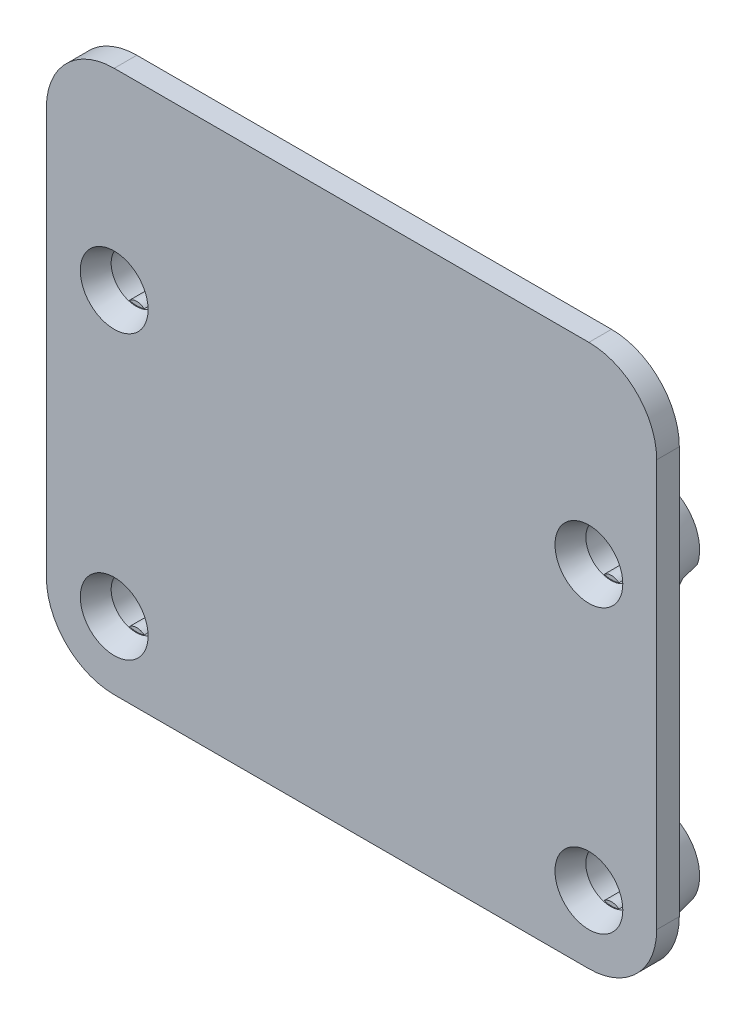
SolidWorks part; units mm, degrees
ref_plane "Front Plane" through (0, 0, 0) normal (0, 0, 1) x (1, 0, 0)
ref_plane "Top Plane" through (0, 0, 0) normal (0, 1, 0) x (1, 0, 0)
ref_plane "Right Plane" through (0, 0, 0) normal (1, 0, 0) x (0, 0, -1)
sketch "Sketch1" plane through (0, 0, 0) normal (0, 0, 1) x (1, 0, 0)
  line L0 (0, 12) -> (0, -12) construction
  line L1 (10.5, 12) -> (-10.5, 12)
  line L2 (13.5, 9) -> (13.5, -9)
  line L3 (10.5, -12) -> (-10.5, -12)
  line L4 (-13.5, 9) -> (-13.5, -9)
  line L5 (10.5, -2.75) -> (-10.5, -2.75) construction
  line L6 (-10.5, -9) -> (-10.5, 3.5) construction
  line L7 (10.5, 3.5) -> (10.5, -9) construction
  arc A0 (-10.5, -12) -> (-13.5, -9) centre (-10.5, -9) cw
  arc A1 (-10.5, 12) -> (-13.5, 9) centre (-10.5, 9) ccw
  arc A2 (10.5, 12) -> (13.5, 9) centre (10.5, 9) cw
  arc A3 (13.5, -9) -> (10.5, -12) centre (10.5, -9) cw
  point P4 (10.5, 3.5)
  point P5 (10.5, -9)
  point P6 (0, 0)
  point P7 (-10.5, -9)
  point P9 (-10.5, 3.5)
  point P17 (-13.5, -12)
  point P20 (-13.5, 12)
  dimension "D4" = 3
  dimension "D1" = 3
  dimension "D2" = 3
  dimension "D3" = 24
  dimension "D5" = 21
  dimension "D6" = 12.5
extrude "Boss-Extrude1" add sketch "Sketch1" along normal blind 1
sketch "Sketch4" plane through (0, 0, 0) normal (0, 0, -1) x (-1, 0, 0)
  circle A0 centre (-10.5, 3.5) radius 2.3
  circle A1 centre (10.5, 3.5) radius 2.3
  circle A2 centre (10.5, -9) radius 2.3
  circle A3 centre (-10.5, -9) radius 2.3
  dimension "D1" = 4.6
extrude "Boss-Extrude2" add sketch "Sketch4" along normal blind 2
hole_wizard "M2 Clearance Hole1" positions "Sketch2" profile "Sketch3" hole size "M2" standard "ISO" end condition through all
sketch "Sketch2" plane through (0, 0, 1) normal (0, 0, 1) x (1, 0, 0)
  point P0 (10.5, 3.5)
  point P2 (10.5, -9)
  point P4 (-10.5, -9)
  point P6 (-10.5, 3.5)
sketch "Sketch3" plane through (10.5, 3.5, 1) normal (1, 0, 0) x (0, -1, 0)
  line L0 (0, 0) -> (0, 3)
  line L1 (0, 3) -> (1.1, 3)
  line L2 (1.1, 3) -> (1.1, 0.9657)
  line L3 (1.1, 0.9657) -> (1.5, 0)
  line L5 (1.5, 0) -> (0, 0)
  line L6 (-1.1, 0.9657) -> (-1.5, 0) construction
  line L11 (0, -6.35) -> (0, 107.95) construction
  dimension "Thru Hole Dia." = 2.2
  dimension "Thru Hole Depth" = 3
  dimension "Near C'Sink Dia." = 3
  dimension "Near C'Sink Angle" = 45
sketch "Sketch6" plane through (0, 0, 1) normal (0, 0, 1) x (1, 0, 0)
  line L0 (8.0915, 2.4) -> (12.5968, 2.4) construction
  line L1 (8.3943, 2.57) -> (12.5968, 2.57) construction
  line L2 (10.5, 3.5) -> (10.5, -9) construction
  line L3 (8.1393, 3.5) -> (12.671, 3.5) construction
  line L4 (8.3943, 4.43) -> (12.5968, 4.43) construction
  line L5 (8.0915, 4.6) -> (12.5968, 4.6) construction
  line L6 (10.1244, 2.4) -> (10.8756, 2.4)
  line L7 (10.1244, 4.6) -> (10.8756, 4.6)
  line L8 (-10.5, -2.75) -> (10.5, -2.75) construction
  line L9 (0, -12) -> (0, 12.0448) construction
  line L10 (-10.5, -12) -> (10.5, -12) construction
  line L11 (10.5, -2.75) -> (-10.5, -2.75) construction
  line L12 (-10.5, -9) -> (-10.5, 3.5) construction
  line L13 (-10.1244, 2.4) -> (-10.8756, 2.4)
  line L14 (-10.1244, 4.6) -> (-10.8756, 4.6)
  line L15 (10.1244, -10.1) -> (10.8756, -10.1)
  line L16 (10.1244, -7.9) -> (10.8756, -7.9)
  line L17 (-10.1244, -10.1) -> (-10.8756, -10.1)
  line L18 (-10.1244, -7.9) -> (-10.8756, -7.9)
  arc A0 (10.8756, 4.6) -> (10.1244, 4.6) centre (10.5, 4.93) cw
  circle A1 centre (10.5, 3.5) radius 1.1 construction
  arc A2 (10.8756, 2.4) -> (10.1244, 2.4) centre (10.5, 2.07) ccw
  arc A3 (-10.8756, 2.4) -> (-10.1244, 2.4) centre (-10.5, 2.07) cw
  arc A4 (-10.8756, 4.6) -> (-10.1244, 4.6) centre (-10.5, 4.93) ccw
  arc A5 (10.8756, -10.1) -> (10.1244, -10.1) centre (10.5, -10.43) ccw
  arc A6 (10.8756, -7.9) -> (10.1244, -7.9) centre (10.5, -7.57) cw
  arc A7 (-10.8756, -10.1) -> (-10.1244, -10.1) centre (-10.5, -10.43) cw
  arc A8 (-10.8756, -7.9) -> (-10.1244, -7.9) centre (-10.5, -7.57) ccw
  dimension "D1" = 1.86
  dimension "D2" = 0.5
extrude "Boss-Extrude3" add sketch "Sketch6" against normal blind 0.75 from offset 1 offset against normal yes
chamfer "Chamfer1" distance 2 distance2 0.4 4 edges at (-12.8, -9, -2) (-12.8, 3.5, -2) (8.2, 3.5, -2) (8.2, -9, -2) first distance on face at (-12.8, -9, -2) first distance on face at (-12.8, 3.5, -2) first distance on face at (8.2, 3.5, -2) first distance on face at (8.2, -9, -2)
sketch "Sketch5" plane through (0, 0, -2) normal (0, 0, -1) x (-1, 0, 0)
  line L0 (8.7126, 4.9474) -> (10.5, 3.5)
  line L1 (10.5, 3.5) -> (9.1808, 1.616)
  line L2 (10.4197, -11.2986) -> (10.5, -9)
  line L3 (10.5, -9) -> (8.2589, -9.5174)
  line L4 (-12.6747, 2.7512) -> (-10.5, 3.5)
  line L5 (-10.5, 3.5) -> (-10.7404, 1.2126)
  line L6 (-10.5, -6.7) -> (-10.5, -9)
  line L7 (-10.5, -9) -> (-8.2004, -8.9599)
  line L8 (-10.5, 3.5) -> (-10.5, -9) construction
  line L9 (10.5, 3.5) -> (10.5, -9) construction
  arc A0 (8.7126, 4.9474) -> (9.1808, 1.616) centre (10.5, 3.5) ccw
  circle A1 centre (10.5, 3.5) radius 2.3 construction
  arc A2 (8.2589, -9.5174) -> (10.4197, -11.2986) centre (10.5, -9) ccw
  circle A3 centre (10.5, -9) radius 2.3 construction
  arc A4 (-10.5, -6.7) -> (-8.2004, -8.9599) centre (-10.5, -9) cw
  circle A5 centre (-10.5, -9) radius 2.3 construction
  arc A6 (-12.6747, 2.7512) -> (-10.7404, 1.2126) centre (-10.5, 3.5) ccw
  circle A7 centre (-10.5, 3.5) radius 2.3 construction
  dimension "D1" = 35
  dimension "D2" = 94
  dimension "D3" = 103
  dimension "D4" = 75
  dimension "D5" = 6
  dimension "D6" = 65
  dimension "D7" = 89
extrude "Cut-Extrude2" cut sketch "Sketch5" against normal blind 0.8
